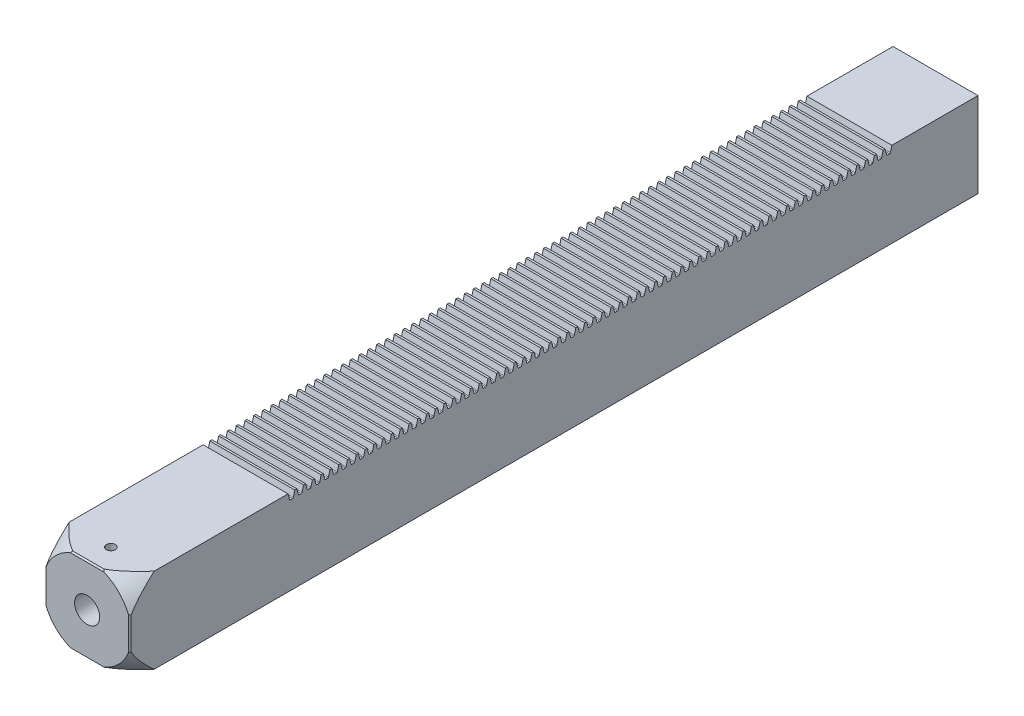
SolidWorks part; units mm, degrees
ref_plane "Front Plane" through (0, 0, 0) normal (0, 0, 1) x (1, 0, 0)
ref_plane "Top Plane" through (0, 0, 0) normal (0, 1, 0) x (1, 0, 0)
ref_plane "Right Plane" through (0, 0, 0) normal (1, 0, 0) x (0, 0, -1)
sketch "Sketch2" plane through (0, 0, 0) normal (0, 0, 1) x (1, 0, 0)
  line L1 (24.13, -24.13) -> (-24.13, -24.13)
  line L2 (24.13, -24.13) -> (24.13, 24.13)
  line L3 (24.13, 24.13) -> (-24.13, 24.13)
  line L4 (-24.13, -24.13) -> (-24.13, 24.13)
  line L5 (24.13, -24.13) -> (-24.13, 24.13) construction
  line L6 (24.13, 24.13) -> (-24.13, -24.13) construction
  point P0 (0, 0)
  dimension "D1" = 48.26
  dimension "D2" = 48.26
extrude "Boss-Extrude1" add sketch "Sketch2" along normal blind 482.6
chamfer "Chamfer1" distance 0.762 angle 45 8 edges at (0, -24.13, 0) (24.13, 0, 0) (0, 24.13, 0) (-24.13, 0, 0) (0, -24.13, 482.6) (-24.13, 0, 482.6) (24.13, 0, 482.6) (0, 24.13, 482.6)
sketch "Sketch4" plane through (24.13, 0, 0) normal (1, 0, 0) x (0, 0, -1)
  line L0 (-53.467, 24.13) -> (-52.6353, 20.9142)
  line L1 (-481.838, 24.13) -> (-0.762, 24.13) construction
  line L2 (-52.1435, 20.5334) -> (-50.9805, 20.5334)
  line L3 (-50.4887, 20.9142) -> (-49.657, 24.13)
  line L4 (-51.562, 20.5334) -> (-51.562, 17.8587) construction
  line L5 (-53.0512, 22.5221) -> (-50.0728, 22.5221) construction
  line L6 (-0.762, -24.13) -> (-0.762, 24.13) construction
  arc A0 (-50.9805, 20.5334) -> (-50.4887, 20.9142) centre (-50.9805, 21.0414) ccw
  arc A1 (-52.6353, 20.9142) -> (-52.1435, 20.5334) centre (-52.1435, 21.0414) ccw
  dimension "D3" = 0.508
  dimension "D1" = 3.5966
  dimension "D2" = 104.5
  dimension "D4" = 3.81
  dimension "D5" = 50.8
extrude "Cut-Extrude1" cut sketch "Sketch4" against normal through all and the other way through all
pattern_linear "LPattern1" count 69 spacing 4.9873 along (0, 0, 1) of "Cut-Extrude1"
hole_wizard "9/16 (0.5625) Diameter Hole1" positions "Sketch6" profile "Sketch7" hole size "9/16" standard "ANSI Inch"
sketch "Sketch6" plane through (0, 0, 482.6) normal (0, 0, 1) x (1, 0, 0)
  point P0 (0, 0)
sketch "Sketch7" plane through (0, 0, 482.6) normal (1, 0, 0) x (0, -1, 0)
  line L0 (0, 0) -> (0, 29.6924)
  line L1 (0, 29.6924) -> (7.1437, 25.4)
  line L2 (7.1437, 25.4) -> (7.1437, 0)
  line L5 (7.1437, 0) -> (0, 0)
  line L10 (0, 29.6924) -> (-7.1438, 25.4) construction
  line L11 (0, -6.35) -> (0, 107.95) construction
  dimension "Hole Dia." = 14.2875
  dimension "Hole Depth" = 25.4
  dimension "Drill Angle" = 118
hole_wizard "1/4-20 Tapped Hole1" positions "Sketch8" profile "Sketch9" tap size "1/4-20" standard "ANSI Inch" end condition up to next
sketch "Sketch8" plane through (0, 24.13, 0) normal (0, 1, 0) x (1, 0, 0)
  line L0 (-24.13, -481.838) -> (24.13, -481.838) construction
  point P0 (0, -469.138)
  dimension "D1" = 12.7
sketch "Sketch9" plane through (0, 24.13, 469.138) normal (1, 0, 0) x (0, 0, 1)
  line L0 (0, 0) -> (0, 16.9862)
  line L1 (0, 16.9862) -> (2.5527, 16.9862)
  line L2 (2.5527, 16.9862) -> (2.5527, 0)
  line L5 (2.5527, 0) -> (0, 0)
  line L11 (0, -6.35) -> (0, 107.95) construction
  dimension "Thru Tap Drill Dia." = 5.1054
  dimension "Thru Tap Drill Depth" = 16.9862
cosmetic thread "Hole Thread1" parameters "D2"=6.35
sketch "Sketch10" plane through (0, 0, 0) normal (1, 0, 0) x (0, 0, -1)
  line L0 (-482.6, 25.2393) -> (-367.5411, 98.5399)
  line L1 (-367.5411, 98.5399) -> (-482.6, 98.5399)
  line L2 (-482.6, 98.5399) -> (-482.6, 25.2393)
  line L3 (-481.838, 24.13) -> (-481.838, -24.13) construction
  line L4 (-481.838, 24.13) -> (-392.6027, 24.13) construction
  line L5 (-303.8804, 0) -> (-275.2399, 0) construction
  point P2 (-481.838, 0)
  dimension "D1" = 32.5
revolve "Cut-Revolve2" cut sketch "Sketch10" angle 360 about L5
